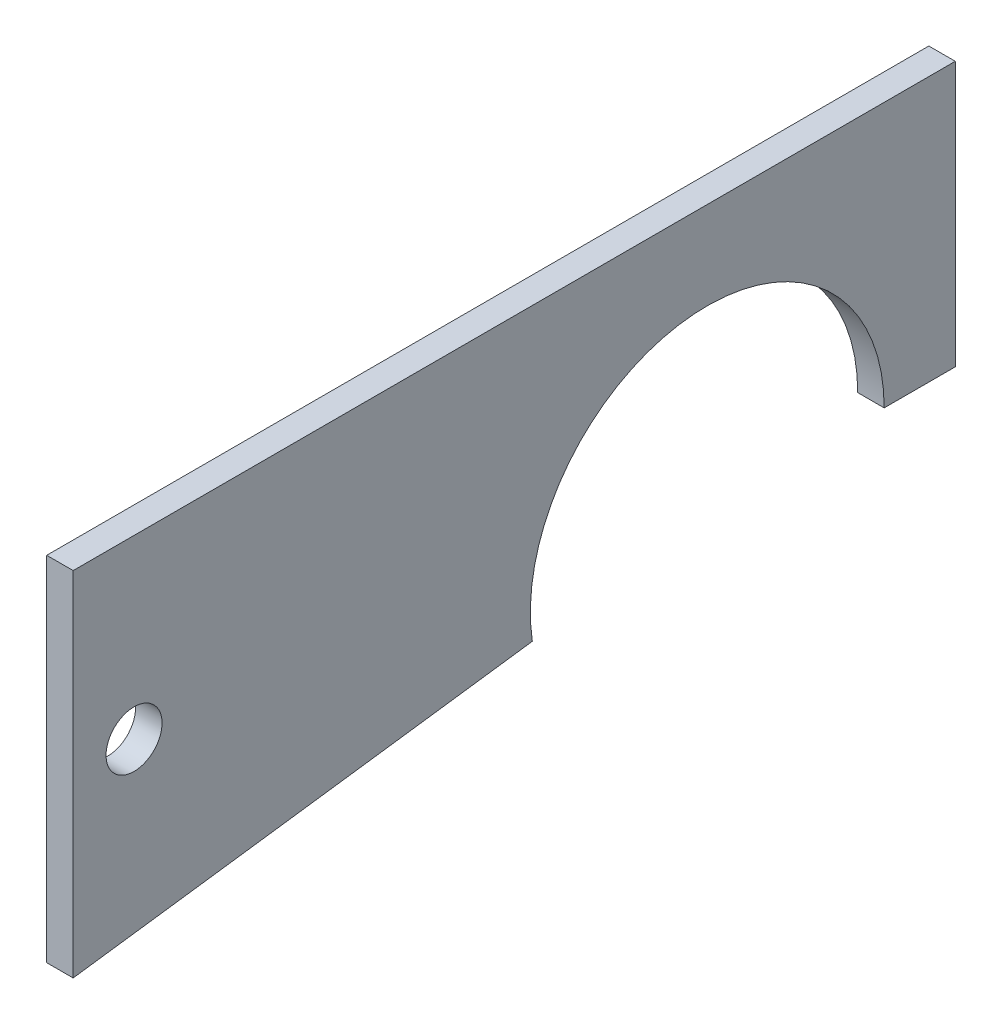
SolidWorks part; units mm, degrees
ref_plane "Front Plane" through (0, 0, 0) normal (0, 0, 1) x (1, 0, 0)
ref_plane "Top Plane" through (0, 0, 0) normal (0, 1, 0) x (1, 0, 0)
ref_plane "Right Plane" through (0, 0, 0) normal (1, 0, 0) x (0, 0, -1)
sketch "Sketch1" plane through (0, 0, 0) normal (1, 0, 0) x (0, 0, -1)
  line L0 (0, 0) -> (100, 0)
  line L3 (52.0493, -32.9727) -> (0, -40)
  line L4 (0, -40) -> (0, 0)
  line L5 (100, 0) -> (100, -30)
  line L6 (100, -30) -> (91.9387, -30)
  arc A0 (52.0493, -32.9727) -> (91.9387, -30) centre (71.8832, -30) cw
  dimension "D1" = 40
  dimension "D2" = 100
  dimension "D3" = 40
  dimension "D4" = 30
extrude "Boss-Extrude1" add sketch "Sketch1" along normal blind 3
sketch "Sketch2" plane through (3, 0, 0) normal (1, 0, 0) x (0, 0, -1)
  line L0 (0, 0) -> (0, -40) construction
  circle A0 centre (6.9009, -20) radius 3.175
  point P4 (0, -20)
  dimension "D1" = 6.35
extrude "Cut-Extrude1" cut sketch "Sketch2" against normal through all
